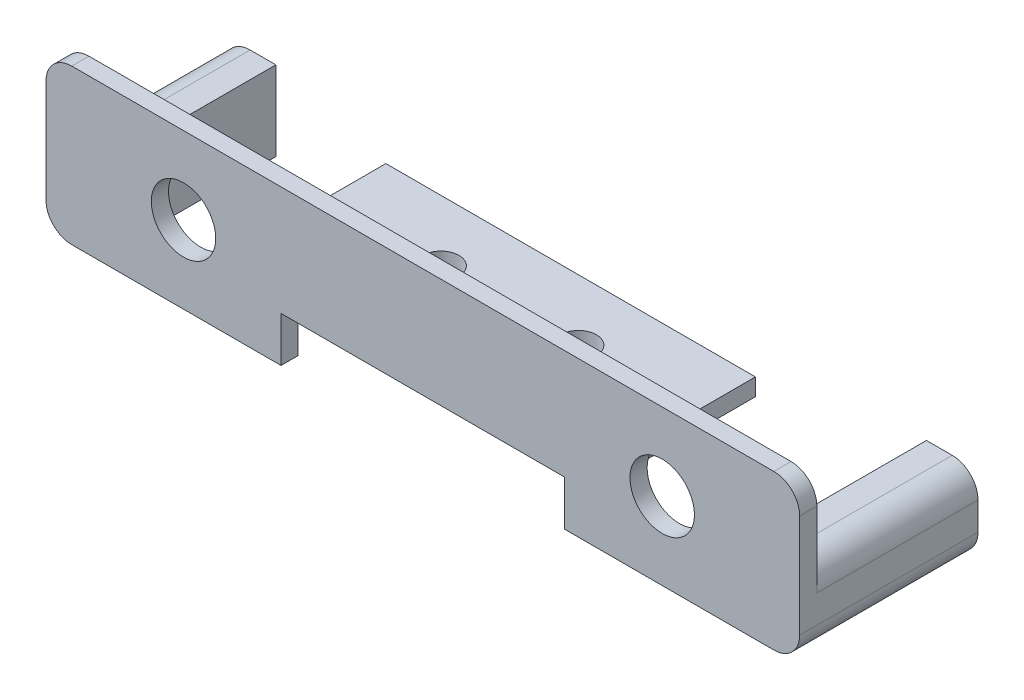
SolidWorks part; units mm, degrees
ref_plane "Front Plane" through (0, 0, 0) normal (0, 0, 1) x (1, 0, 0)
ref_plane "Top Plane" through (0, 0, 0) normal (0, 1, 0) x (1, 0, 0)
ref_plane "Right Plane" through (0, 0, 0) normal (1, 0, 0) x (0, 0, -1)
sketch "Sketch3" plane through (0, 0, 0) normal (0, 1, 0) x (1, 0, 0)
  line L1 (-21.5, 0) -> (21.5, 0)
  line L2 (-21.5, 0) -> (-21.5, 15.2)
  line L3 (-21.5, 15.2) -> (21.5, 15.2)
  line L4 (21.5, 0) -> (21.5, 15.2)
  line L5 (-8, 8.1) -> (8, 8.1) construction
  circle A0 centre (-8, 8.1) radius 2.1
  circle A1 centre (8, 8.1) radius 2.1
  point P6 (0, 0)
  point P12 (0, 8.1)
  dimension "D2" = 4.2
  dimension "D1" = 16
  dimension "D3" = 5
  dimension "D4" = 6
  dimension "D5" = 43
extrude "Boss-Extrude5" add sketch "Sketch3" against normal blind 2 separate body
sketch "Sketch1" plane through (0, 0, 0) normal (0, 0, 1) x (1, 0, 0)
  line L0 (0, -1000) -> (0, 49000) construction
  line L1 (-43.85, -9.25) -> (-16.5, -9.25)
  line L2 (-43.85, -9.25) -> (-43.85, 8.75)
  line L4 (43.85, -9.25) -> (43.85, 8.75)
  line L5 (-43.85, -0.25) -> (43.85, -0.25) construction
  line L6 (-43.85, 8.75) -> (43.85, 8.75)
  line L15 (-37.85, -24) -> (-37.85, 0) construction
  line L17 (-16.5, -9.25) -> (-16.5, -4)
  line L18 (-16.5, -4) -> (16.5, -4)
  line L19 (16.5, -4) -> (16.5, -9.25)
  line L20 (16.5, -9.25) -> (43.85, -9.25)
  line L22 (-21.5, -2) -> (21.5, -2) construction
  line L23 (-21.5, 0) -> (21.5, 0) construction
  line L24 (-21.5, -2) -> (-21.5, 0) construction
  circle A0 centre (-27.85, -0.25) radius 3.75
  circle A2 centre (27.85, -0.25) radius 3.75
  point P14 (0, -4)
  dimension "D3" = 7.5
  dimension "D4" = 10
  dimension "D1" = 18
  dimension "D2" = 6
  dimension "D5" = 5
  dimension "D6" = 2
  dimension "D7" = 4
extrude "Boss-Extrude1" add sketch "Sketch1" along normal blind 2
chamfer "Chamfer1" distance 1.5 angle 45 1 edges at (0, -2, 0)
sketch "Sketch5" plane through (0, 0, 0) normal (0, 0, -1) x (-1, 0, 0)
  line L0 (43.85, -9.25) -> (16.5, -9.25) construction
  line L1 (43.85, 0) -> (37.85, 0)
  line L2 (43.85, 0) -> (43.85, -9.25)
  line L3 (43.85, -9.25) -> (37.85, -9.25)
  line L4 (37.85, 0) -> (37.85, -9.25)
  line L5 (37.85, -24) -> (37.85, 0) construction
  line L6 (37.85, 0) -> (60.85, 0) construction
extrude "Boss-Extrude4" add sketch "Sketch5" along normal up to surface (18.75 mm away)
mirror "Mirror2" about plane through (0, 0, 0) normal (1, 0, 0) of "Boss-Extrude4"
fillet "Fillet1" radius 3 6 edges at (43.85, 8.75, 1) (-43.85, -9.25, -8.375) (-43.85, 8.75, 1) (-43.85, 0, -9.375) (43.85, 0, -9.375) (43.85, -9.25, -8.375)
equation "\"width\"= 24"
equation "\"thk\"= 3"
equation "\"holesize\"= 4.2"
equation "\"holedistance\"= ( 20 + 12 ) / 2"
equation "\"threaded_hole\"= 3.9"
equation "\"fillet_radius\"= 2"
equation "\"ground_clearance\"= 25"
equation "\"tire_thk\"= 3"
equation "\"innerwheel_diam\" = \"wheel_diam\"-2*\"tire_thk\""
equation "\"innerwheel_thk\"= 8"
equation "\"wheel_diam\"= 2*(\"width\"/2+\"ground_clearance\")"
equation "\"coloursensor_holesize\"= 2.65"
equation "\"hole_to_edge\" = 4"
equation "\"D1@Sketch3\"=\"holedistance\""
equation "\"D2@Sketch3\"=\"holesize\""
